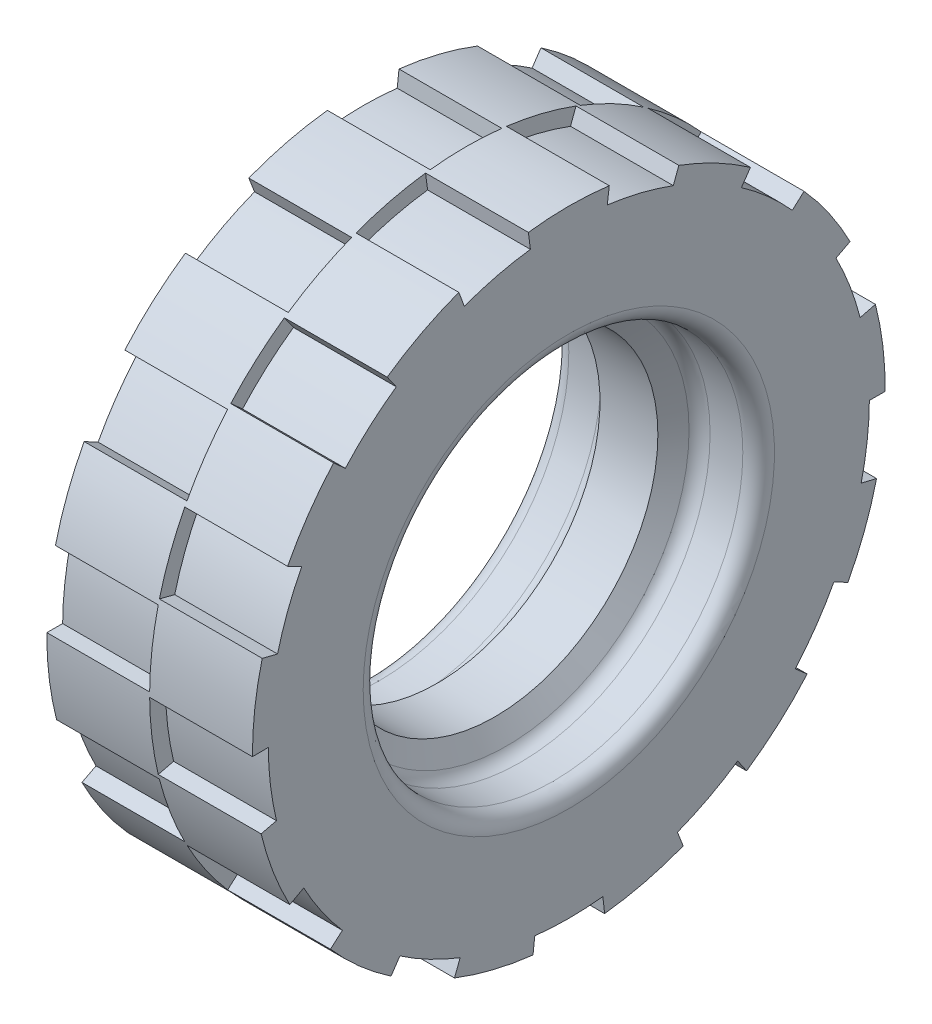
SolidWorks part; units mm, degrees
material "BUTYL"
ref_plane "Front" through (0, 0, 0) normal (0, 0, 1) x (1, 0, 0)
ref_plane "Top" through (0, 0, 0) normal (0, 1, 0) x (1, 0, 0)
ref_plane "Right" through (0, 0, 0) normal (1, 0, 0) x (0, 0, -1)
sketch "Sketch1" plane through (0, 0, 0) normal (0, 0, 1) x (1, 0, 0)
  line L0 (0, 0) -> (0, 10) construction
  line L1 (-3.25, 10) -> (3.25, 10)
  line L2 (0, 0) -> (6.4758, 0) construction
  line L3 (3.25, 10) -> (3.25, 6)
  line L4 (3.25, 6) -> (1.435, 6)
  line L5 (1.435, 6) -> (0.915, 5.15)
  line L6 (-0.915, 5.15) -> (0.915, 5.15)
  line L7 (-1.435, 6) -> (-0.915, 5.15)
  line L8 (-3.25, 6) -> (-1.435, 6)
  line L9 (-3.25, 10) -> (-3.25, 6)
  point P10 (0, 5.15)
  dimension "D1" = 3.25
  dimension "D2" = 20
  dimension "D3" = 12
  dimension "D4" = 10.3
  dimension "D5" = 2.87
  dimension "D6" = 1.83
revolve "Revolve1" add sketch "Sketch1" angle 360 about L2
sketch "Sketch2" plane through (-3.25, 0, 0) normal (-1, 0, 0) x (0, 0, 1)
  line L0 (0, 0) -> (0, 14.0412) construction
  line L1 (-1.0754, 9.4389) -> (-1.132, 9.9357)
  line L2 (1.0754, 9.4389) -> (1.132, 9.9357)
  circle A1 centre (0, 0) radius 10 construction
  circle A2 centre (0, 0) radius 9.5
  arc A3 (1.0754, 9.4389) -> (-1.0754, 9.4389) centre (0, 0) ccw
  arc A4 (1.132, 9.9357) -> (-1.132, 9.9357) centre (0, 0) ccw
  dimension "D1" = 0.5
extrude "Cut-Extrude1" cut sketch "Sketch2" against normal blind 3.25
pattern_circular "CirPattern1" count 13 over 360 about axis through (-3.25, 0, 0) along (-1, 0, 0) of "Cut-Extrude1"
sketch "Sketch3" plane through (3.25, 0, 0) normal (1, 0, 0) x (0, 0, -1)
  line L0 (-3.3029, 8.9074) -> (-3.4767, 9.3762)
  line L1 (0, 0) -> (-3.326, 13.4955) construction
  line L2 (-1.2145, 9.422) -> (-1.2784, 9.9179)
  circle A0 centre (0, 0) radius 10 construction
  arc A1 (-1.2784, 9.9179) -> (-3.4767, 9.3762) centre (0, 0) ccw
  arc A2 (-1.2145, 9.422) -> (-3.3029, 8.9074) centre (0, 0) ccw
  circle A3 centre (0, 0) radius 9.5 construction
  circle A4 centre (0, 0) radius 10 construction
  dimension "D1" = 0.5
extrude "Cut-Extrude2" cut sketch "Sketch3" against normal blind 3.25
pattern_circular "CirPattern2" count 13 over 360 about axis through (3.25, 0, 0) along (-1, 0, 0) of "Cut-Extrude2"
fillet "Fillet1" radius 0.5 4 edges at (3.25, 0, 6) (-3.25, 0, 6) (1.435, 0, 6) (-1.435, 0, 6)
